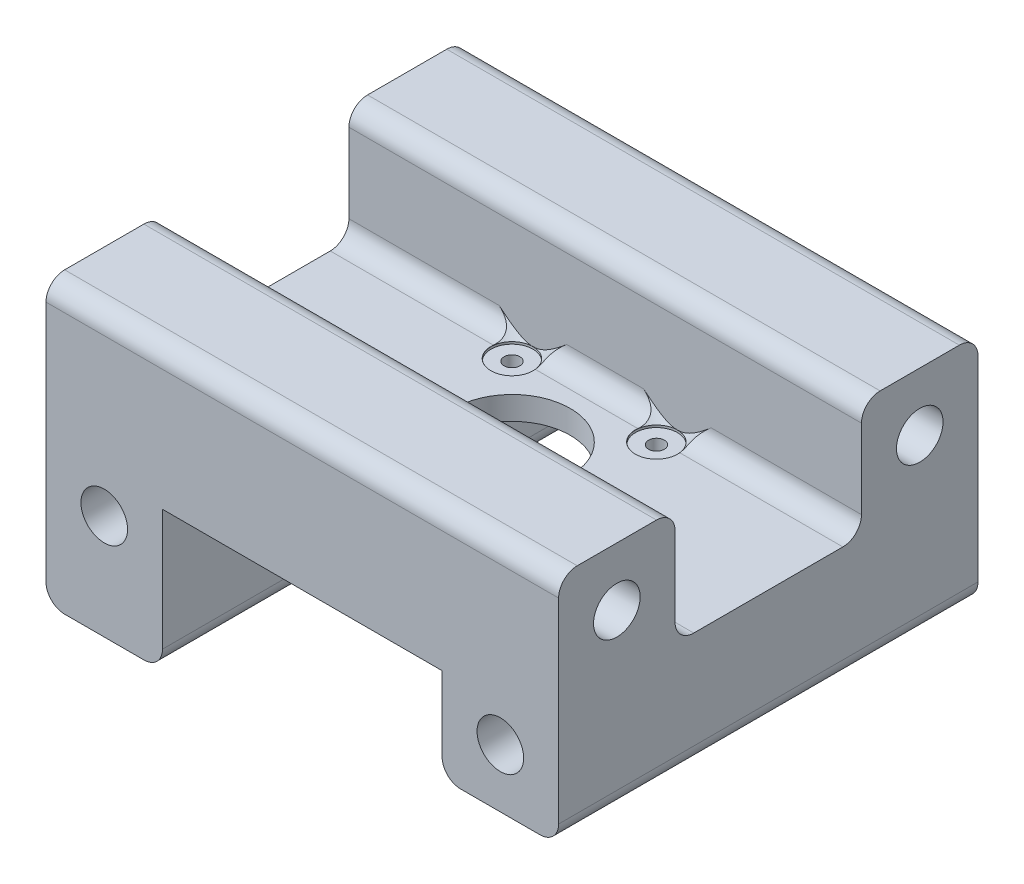
SolidWorks part; units mm, degrees
ref_plane "Front Plane" through (0, 0, 0) normal (0, 0, 1) x (1, 0, 0)
ref_plane "Top Plane" through (0, 0, 0) normal (0, 1, 0) x (1, 0, 0)
ref_plane "Right Plane" through (0, 0, 0) normal (1, 0, 0) x (0, 0, -1)
sketch "Sketch1" plane through (0, 0, 0) normal (0, 1, 0) x (1, 0, 0)
  line L1 (-94.6161, 38.7066) -> (15.3839, 38.7066)
  line L2 (-94.6161, 38.7066) -> (-94.6161, -51.2934)
  line L3 (-94.6161, -51.2934) -> (15.3839, -51.2934)
  line L4 (15.3839, 38.7066) -> (15.3839, -51.2934)
  dimension "D1" = 110
  dimension "D2" = 90
extrude "Boss-Extrude2" add sketch "Sketch1" along normal blind 35
sketch "Sketch2" plane through (0, 35, 0) normal (0, 1, 0) x (1, 0, 0)
  line L0 (15.3839, -51.2934) -> (15.3839, 38.7066) construction
  line L2 (-94.6161, 38.7066) -> (15.3839, 38.7066)
  line L3 (-94.6161, 38.7066) -> (-94.6161, 13.7066)
  line L4 (-94.6161, 13.7066) -> (15.3839, 13.7066)
  line L5 (15.3839, 38.7066) -> (15.3839, 13.7066)
  line L6 (-94.6161, -51.2934) -> (15.3839, -51.2934)
  line L7 (-94.6161, -51.2934) -> (-94.6161, -26.2934)
  line L8 (-94.6161, -26.2934) -> (15.3839, -26.2934)
  line L9 (15.3839, -51.2934) -> (15.3839, -26.2934)
  dimension "D1" = 25
  dimension "D2" = 25
extrude "Boss-Extrude3" add sketch "Sketch2" along normal blind 25
sketch "Sketch3" plane through (-94.6161, 0, 0) normal (-1, 0, 0) x (0, 0, 1)
  line L0 (-38.7066, 60) -> (-38.7066, 0) construction
  line L1 (-13.7066, 60) -> (-13.7066, 35) construction
  line L2 (-38.7066, 60) -> (-13.7066, 60) construction
  line L3 (-13.7066, 35) -> (26.2934, 35) construction
  line L4 (51.2934, 60) -> (51.2934, 0) construction
  line L5 (26.2934, 60) -> (51.2934, 60) construction
  circle A0 centre (-26.2066, 47.5) radius 7.5
  circle A1 centre (38.7934, 47.5) radius 7.5
  dimension "D1" = 15
  dimension "D6" = 15
  dimension "D2" = 12.5
  dimension "D3" = 12.5
  dimension "D4" = 12.5
  dimension "D5" = 12.5
  dimension "D7" = 12.5
  dimension "D8" = 12.5
extrude "Cut-Extrude1" cut sketch "Sketch3" against normal blind 45
sketch "Sketch4" plane through (0, 0, 51.2934) normal (0, 0, 1) x (1, 0, 0)
  line L0 (-94.6161, 60) -> (-94.6161, 0) construction
  line L2 (-94.6161, 60) -> (15.3839, 60) construction
  line L5 (15.3839, 60) -> (15.3839, 0) construction
  circle A0 centre (-82.1161, 22.5) radius 5
  circle A2 centre (2.8839, 22.5) radius 5
  dimension "D1" = 10
  dimension "D4" = 10
  dimension "D2" = 12.5
  dimension "D3" = 37.5
  dimension "D6" = 12.5
extrude "Cut-Extrude2" cut sketch "Sketch4" against normal blind 90
sketch "Sketch5" plane through (0, 0, 51.2934) normal (0, 0, 1) x (1, 0, 0)
  line L0 (15.3839, 60) -> (15.3839, 0) construction
  line L1 (-69.6161, 30) -> (-9.6161, 30)
  line L2 (-69.6161, 30) -> (-69.6161, 0)
  line L3 (-69.6161, 0) -> (-9.6161, 0)
  line L4 (-9.6161, 30) -> (-9.6161, 0)
  line L5 (-94.6161, 0) -> (15.3839, 0) construction
  circle A1 centre (-82.1161, 22.5) radius 5 construction
  dimension "D1" = 25
  dimension "D2" = 12.5
  dimension "D3" = 30
  dimension "D4" = 0
  dimension "D5" = 30
extrude "Cut-Extrude3" cut sketch "Sketch5" against normal blind 90 contours L2 L1 L4 L3
sketch "Sketch6" plane through (0, 0, 0) normal (0, -1, 0) x (1, 0, 0)
  line L1 (-94.6161, 51.2934) -> (15.3839, 51.2934)
  line L2 (-94.6161, 51.2934) -> (-94.6161, -38.7066)
  line L3 (-94.6161, -38.7066) -> (15.3839, -38.7066)
  line L4 (15.3839, 51.2934) -> (15.3839, -38.7066)
sketch "Sketch7" plane through (0, 35, 0) normal (0, 1, 0) x (1, 0, 0)
  line L0 (-94.6161, 13.7066) -> (15.3839, 13.7066) construction
  line L1 (-69.6161, 13.7066) -> (-9.6161, 13.7066)
  line L2 (-69.6161, 13.7066) -> (-69.6161, -26.2934)
  line L3 (-69.6161, -26.2934) -> (-9.6161, -26.2934)
  line L4 (-9.6161, 13.7066) -> (-9.6161, -26.2934)
  line L5 (15.3839, -26.2934) -> (-94.6161, -26.2934) construction
  line L6 (15.3839, -26.2934) -> (15.3839, 13.7066) construction
  line L7 (-94.6161, 13.7066) -> (-94.6161, -26.2934) construction
  circle A0 centre (-39.6161, -6.2934) radius 12.5
  dimension "D5" = 25
  dimension "D1" = 25
  dimension "D2" = 25
  dimension "D3" = 60
  dimension "D4" = 30
  dimension "D6" = 20
extrude "Cut-Extrude4" cut sketch "Sketch7" against normal blind 5 contours A0
sketch "Sketch8" plane through (0, 35, 0) normal (0, 1, 0) x (1, 0, 0)
  line L0 (-94.6161, 13.7066) -> (15.3839, 13.7066) construction
  line L1 (-69.6161, 13.7066) -> (-9.6161, 13.7066)
  line L2 (-69.6161, 13.7066) -> (-69.6161, -26.2934)
  line L3 (-69.6161, -26.2934) -> (-9.6161, -26.2934)
  line L4 (-9.6161, 13.7066) -> (-9.6161, -26.2934)
  line L5 (15.3839, -26.2934) -> (-94.6161, -26.2934) construction
  line L6 (15.3839, -26.2934) -> (15.3839, 13.7066) construction
  line L7 (-94.6161, 13.7066) -> (-94.6161, -26.2934) construction
  circle A0 centre (-27.1161, -19.5184) radius 1.5282
  circle A1 centre (-39.6161, -6.2934) radius 12.5 construction
  dimension "D3" = 12.5
  dimension "D1" = 25
  dimension "D2" = 25
sketch "Sketch9" plane through (0, 35, 0) normal (0, 1, 0) x (1, 0, 0)
  line L3 (-55.1161, 9.2066) -> (-24.1161, 9.2066) construction
  line L4 (-55.1161, 9.2066) -> (-55.1161, -21.7934) construction
  line L5 (-55.1161, -21.7934) -> (-24.1161, -21.7934) construction
  line L6 (-24.1161, 9.2066) -> (-24.1161, -21.7934) construction
  line L7 (-55.1161, 9.2066) -> (-24.1161, -21.7934) construction
  line L8 (-55.1161, -21.7934) -> (-24.1161, 9.2066) construction
  circle A4 centre (-55.1161, 9.2066) radius 1.5
  circle A5 centre (-24.1161, 9.2066) radius 1.5
  circle A6 centre (-24.1161, -21.7934) radius 1.5
  circle A7 centre (-55.1161, -21.7934) radius 1.5
  point P8 (-39.6161, -6.2934)
  dimension "D1" = 3
  dimension "D2" = 31
  dimension "D3" = 31
  dimension "D4" = 2
  dimension "D5" = 2
extrude "Cut-Extrude5" cut sketch "Sketch9" against normal blind 5
sketch "Sketch11" plane through (0, 0, 0) normal (0, -1, 0) x (1, 0, 0)
  line L1 (-94.6161, 51.2934) -> (-69.6161, 51.2934)
  line L2 (-94.6161, 51.2934) -> (-94.6161, -38.7066)
  line L3 (-94.6161, -38.7066) -> (-69.6161, -38.7066)
  line L4 (-69.6161, 51.2934) -> (-69.6161, -38.7066)
sketch "Sketch12" plane through (0, 0, 0) normal (0, -1, 0) x (1, 0, 0)
  line L1 (-9.6161, 51.2934) -> (15.3839, 51.2934)
  line L2 (-9.6161, 51.2934) -> (-9.6161, -38.7066)
  line L3 (-9.6161, -38.7066) -> (15.3839, -38.7066)
  line L4 (15.3839, 51.2934) -> (15.3839, -38.7066)
extrude "Cut-Extrude6" cut sketch "Sketch12" against normal blind 10
sketch "Sketch13" plane through (-94.6161, 0, 0) normal (-1, 0, 0) x (0, 0, 1)
  line L0 (51.2934, 0) -> (-38.7066, 0) construction
  line L4 (-13.7066, 60) -> (-13.7066, 35) construction
  line L5 (26.2934, 60) -> (26.2934, 35) construction
  circle A0 centre (10.2934, 10) radius 1.5
  circle A1 centre (2.2934, 10) radius 1.5
  dimension "D4" = 3
  dimension "D5" = 3
  dimension "D1" = 10
  dimension "D2" = 16
  dimension "D3" = 16
extrude "Cut-Extrude7" cut sketch "Sketch13" against normal up to next
sketch "Sketch14" plane through (0, 35, 0) normal (0, 1, 0) x (1, 0, 0)
  point P0 (-55.1161, 9.2066)
  point P3 (-24.1161, 9.2066)
  point P6 (-24.1161, -21.7934)
  point P9 (-55.1161, -21.7934)
hole_wizard "CBORE for M3 Hexagon head bolts-Full thread-grades AB1" positions "Sketch14" profile "Sketch15" counterbore size "M3" standard "GB" end condition through all
sketch "Sketch15" plane through (-55.1161, 35, -9.2066) normal (1, 0, 0) x (0, 0, 1)
  line L0 (0, 0) -> (0, 35)
  line L1 (0, 35) -> (1.7, 35)
  line L3 (1.7, 35) -> (1.7, 0.5)
  line L4 (4.5, 0.5) -> (1.7, 0.5)
  line L5 (4.5, 0.5) -> (4.5, 0.025)
  line L6 (4.5, 0.025) -> (4.525, 0)
  line L7 (4.525, 0) -> (0, 0)
  line L8 (-4.5, 0.025) -> (-4.525, 0) construction
  line L11 (0, -6.35) -> (0, 107.95) construction
  dimension "Thru Hole Dia." = 3.4
  dimension "Thru Hole Depth" = 35
  dimension "C'Bore Dia." = 9
  dimension "C'Bore Depth" = 0.5
  dimension "Near C'Sink Dia." = 9.05
  dimension "Near C'Sink Angle" = 90
fillet "Fillet1" radius 4 14 edges at (15.3839, 10, 6.2934) (-9.6161, 10, 6.2934) (-69.6161, 0, 6.2934) (-94.6161, 0, 6.2934) (-4.1286, 35, 26.2934) (-75.1036, 35, 26.2934) (-75.1036, 35, -13.7066) (-4.1286, 35, -13.7066) (-39.6161, 60, 51.2934) (-39.6161, 60, 26.2934) (-39.6161, 60, -13.7066) (-39.6161, 60, -38.7066) (-39.6161, 35, -13.7066) (-39.6161, 35, 26.2934)
sketch "Sketch16" plane through (15.3839, 0, 0) normal (1, 0, 0) x (0, 0, -1)
  circle A0 centre (26.2066, 47.5) radius 5
  dimension "D1" = 10
extrude "Cut-Extrude8" cut sketch "Sketch16" against normal blind 35 contours A0
sketch "Sketch19" plane through (-49.6161, 0, 0) normal (-1, 0, 0) x (0, 0, 1)
  circle A0 centre (38.7934, 47.5) radius 5
  dimension "D1" = 10
extrude "Cut-Extrude9" cut sketch "Sketch19" against normal blind 66
sketch "Sketch20" plane through (-49.6161, 0, 0) normal (-1, 0, 0) x (0, 0, 1)
  circle A0 centre (-26.2066, 47.5) radius 5
  dimension "D1" = 10
extrude "Cut-Extrude10" cut sketch "Sketch20" against normal blind 88
sketch "Sketch21" plane through (0, 0, -38.7066) normal (0, 0, -1) x (-1, 0, 0)
  circle A0 centre (82.1161, 22.5) radius 7.5
extrude "Cut-Extrude11" cut sketch "Sketch21" against normal blind 45
sketch "Sketch22" plane through (0, 0, -38.7066) normal (0, 0, -1) x (-1, 0, 0)
  circle A0 centre (-2.8839, 22.5) radius 7.5
extrude "Cut-Extrude12" cut sketch "Sketch22" against normal blind 45 contours A0
sketch "Sketch23" plane through (0, 35, 0) normal (0, 1, 0) x (1, 0, 0)
  circle A0 centre (-73.1398, -17.0932) radius 2.5
  point P2 (-72.1835, 0)
  point P3 (-72.3765, -16.8998)
  point P4 (-73.7572, -17.0253)
  point P5 (-73.1398, -17.0932)
extrude "Cut-Extrude13" cut sketch "Sketch23" against normal blind 15 contours A0
fillet "Fillet2" radius 2 1 edges at (-94.6161, 47.5, -18.7066) type face fillet first side face at (-49.6161, 47.5, -18.7066) second side face at (-94.6161, 10, 11.7934)
fillet "Fillet3" radius 2 1 edges at (-94.6161, 47.5, 46.2934) type face fillet first side face at (-49.6161, 47.5, 46.2934) second side face at (-94.6161, 47.5, -35.7066)
fillet "Fillet4" radius 2 1 edges at (-4.6161, 22.5, -38.7066) type face fillet first side face at (-4.6161, 22.5, -38.7066) second side face at (-4.6161, 22.5, 6.2934)
fillet "Fillet5" radius 2 1 edges at (-89.6161, 22.5, -38.7066) type face fillet first side face at (-89.6161, 22.5, 6.2934) second side face at (12.3839, 22.5, -38.7066)
